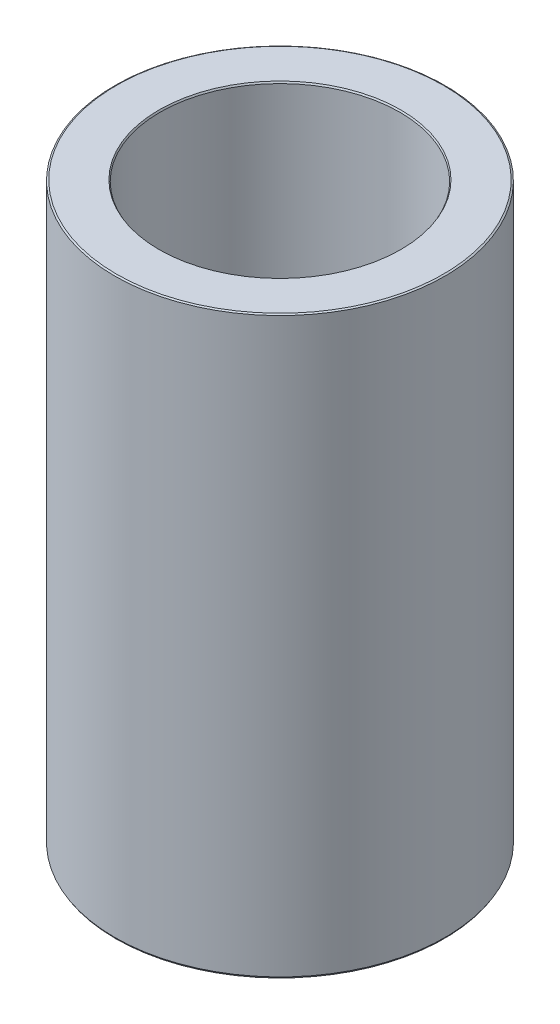
SolidWorks part; units mm, degrees
ref_plane "Front Plane" through (0, 0, 0) normal (0, 0, 1) x (1, 0, 0)
ref_plane "Top Plane" through (0, 0, 0) normal (0, 1, 0) x (1, 0, 0)
ref_plane "Right Plane" through (0, 0, 0) normal (1, 0, 0) x (0, 0, -1)
sketch "Sketch1" plane through (0, 0, 0) normal (0, 1, 0) x (1, 0, 0)
  circle A0 centre (0, 0) radius 52.5
  dimension "SLEEVE_OD" = 105
extrude "Boss-Extrude1" add sketch "Sketch1" along normal blind 182.9374
sketch "Sketch2" plane through (0, 0, 0) normal (0, 1, 0) x (1, 0, 0)
  circle A0 centre (0, 0) radius 38.1729
  dimension "BORE_D" = 76.3458
extrude "Cut-Extrude1" cut sketch "Sketch2" along normal through all
chamfer "Chamfer1" distance 0.2901 angle 60 4 edges at (0, 182.9374, 38.1729) (0, 0, 38.1729) (0, 0, 52.5) (0, 182.9374, 52.5) first distance on face at (0, 182.9374, 38.1729) first distance on face at (0, 0, 38.1729) first distance on face at (0, 182.9374, 52.5)
